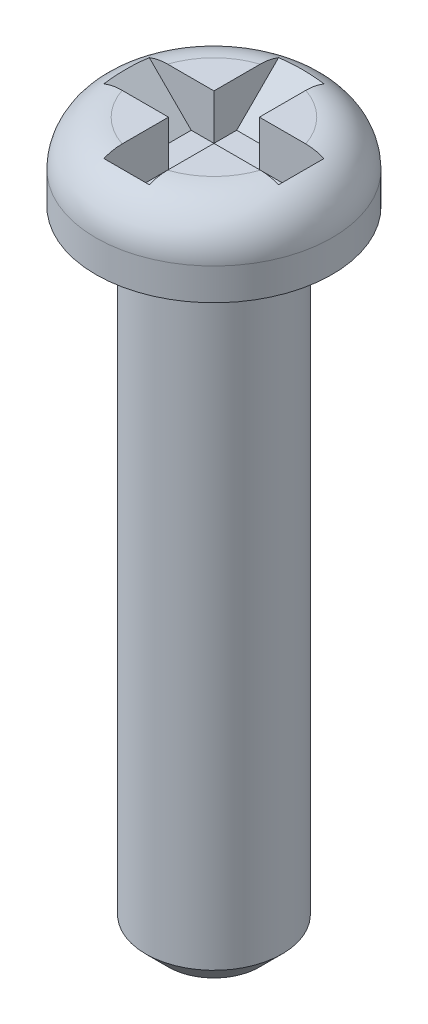
SolidWorks part; units mm, degrees
ref_plane "前视基准面" through (0, 0, 0) normal (0, 0, 1) x (1, 0, 0)
ref_plane "上视基准面" through (0, 0, 0) normal (0, 1, 0) x (1, 0, 0)
ref_plane "右视基准面" through (0, 0, 0) normal (1, 0, 0) x (0, 0, -1)
other "Configuration Table"
sketch "草图1" plane through (0, 0, 0) normal (0, 1, 0) x (1, 0, 0)
  circle A0 centre (0, 0) radius 1.5
  dimension "D1" = 3
extrude "凸台-拉伸1" add sketch "草图1" along normal blind 14
cosmetic thread "装饰螺纹线1" parameters "D2"=3
sketch "草图2" plane through (0, 14, 0) normal (0, 1, 0) x (1, 0, 0)
  circle A0 centre (0, 0) radius 2.6
  dimension "D1" = 5.2
extrude "凸台-拉伸2" add sketch "草图2" along normal blind 1.7
fillet "圆角1" radius 1 1 edges at (0, 15.7, 2.6)
chamfer "倒角1" distance 0.5 angle 45 1 edges at (0, 0, 1.5)
sketch "草图3" plane through (0, 15.7, 0) normal (0, 1, 0) x (1, 0, 0)
  line L0 (-2, 0) -> (2, 0)
  line L1 (0, 2) -> (0, -2)
  point P5 (0, 0)
  point P9 (0, 0)
  dimension "D1" = 4
  dimension "D2" = 4
extrude "切除-拉伸-薄壁1" cut sketch "草图3" against normal blind 1 thin thin type mid plane wall 1
chamfer "倒角2" distance 1 angle 45 4 edges at (0, 14.7, 2) (2, 14.7, 0) (0, 14.7, -2) (-2, 14.7, 0)
